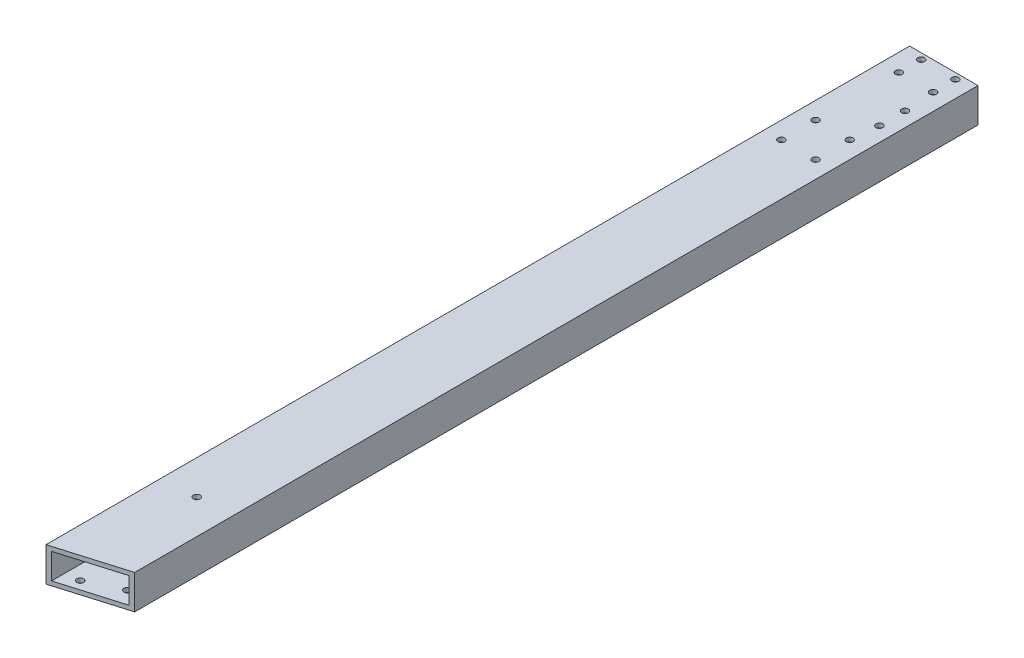
SolidWorks part; units mm, degrees
material "1060 Alloy"
ref_plane "Front Plane" through (0, 0, 0) normal (0, 0, 1) x (1, 0, 0)
ref_plane "Top Plane" through (0, 0, 0) normal (0, 1, 0) x (1, 0, 0)
ref_plane "Right Plane" through (0, 0, 0) normal (1, 0, 0) x (0, 0, -1)
sketch "Sketch1" plane through (0, 0, 0) normal (0, 0, 1) x (1, 0, 0)
  line L0 (-22.225, 9.525) -> (22.225, 9.525)
  line L2 (-25.4, 12.7) -> (25.4, 12.7)
  line L3 (-25.4, 12.7) -> (-25.4, -12.7)
  line L4 (-25.4, -12.7) -> (25.4, -12.7)
  line L5 (25.4, 12.7) -> (25.4, -12.7)
  line L10 (22.225, 9.525) -> (22.225, -9.525)
  line L11 (-22.225, -9.525) -> (22.225, -9.525)
  line L12 (-22.225, 9.525) -> (-22.225, -9.525)
  point P12 (0, 12.7)
  point P14 (25.4, 0)
  dimension "Wall Thickness" = 3.175
  dimension "Outside Width" = 50.8
  dimension "Outside Height" = 25.4
  dimension "Inside Height" = 19.05
  dimension "Inside Width" = 44.45
sketch "Sketch2" plane through (0, 0, 0) normal (1, 0, 0) x (0, 0, -1)
  line L0 (320.675, 0) -> (-320.675, 0)
  point P4 (0, 0)
  point P7 (-320.675, 0)
  point P10 (320.675, 0)
  dimension "Length" = 641.35
sketch "Sketch3" plane through (0, 0, 0) normal (0, 0, 1) x (1, 0, 0)
  line L21 (25.4, 12.7) -> (-25.4, 12.7)
  line L22 (25.4, -12.7) -> (25.4, 12.7)
  line L23 (-25.4, -12.7) -> (25.4, -12.7)
  line L24 (-25.4, 12.7) -> (-25.4, -12.7)
  line L25 (25.4, 12.7) -> (-25.4, 12.7)
  line L26 (25.4, -12.7) -> (25.4, 12.7)
  line L27 (-25.4, -12.7) -> (25.4, -12.7)
  line L28 (-25.4, 12.7) -> (-25.4, -12.7)
  line L29 (22.225, 9.525) -> (-22.225, 9.525)
  line L30 (22.225, -9.525) -> (22.225, 9.525)
  line L31 (-22.225, -9.525) -> (22.225, -9.525)
  line L32 (-22.225, 9.525) -> (-22.225, -9.525)
  line L33 (22.225, 9.525) -> (-22.225, 9.525)
  line L34 (22.225, -9.525) -> (22.225, 9.525)
  line L35 (-22.225, -9.525) -> (22.225, -9.525)
  line L36 (-22.225, 9.525) -> (-22.225, -9.525)
  dimension "D1" = 0
  dimension "D2" = 0
extrude "Boss-Extrude1" add sketch "Sketch3" along normal up to vertex (320.675 mm away) and the other way up to vertex (320.675 mm away) up to point (0, 0, 320.675) other way up to point (0, 0, -320.675)
sketch "Drawing Reference" plane through (0, 0, 0) normal (1, 0, 0) x (0, 0, -1)
  line L0 (-320.675, 0) -> (320.675, 0) construction
  line L1 (0, -12.7) -> (0, 12.7) construction
  line L2 (-320.675, -12.7) -> (320.675, -12.7) construction
  line L5 (-320.675, 12.7) -> (320.675, 12.7) construction
  point P7 (-284.099, 0)
  point P8 (284.099, 0)
  dimension "D1" = 36.576
sketch "Sketch4" plane through (0, 12.7, 0) normal (0, 1, 0) x (1, 0, 0)
  line L0 (-25.4, -320.675) -> (25.4, -305.6274)
  line L1 (25.4, -320.675) -> (25.4, 320.675) construction
  line L2 (25.4, -320.675) -> (-25.4, -320.675)
  dimension "D1" = 16.5
extrude "Cut-Extrude1" cut sketch "Sketch4" against normal through all and the other way through all flip side to cut
sketch "Sketch6" plane through (0, -12.7, 0) normal (0, -1, 0) x (1, 0, 0)
  line L0 (25.4, 305.6274) -> (22.1108, 294.5233) construction
  line L1 (25.4, 279.2824) -> (22.225, 279.2824) construction
  line L2 (25.4, 305.6274) -> (25.4, -320.675) construction
  line L3 (22.225, 279.2824) -> (22.225, 313.1512) construction
  line L4 (22.1108, 294.5233) -> (11.811, 297.5742) construction
  line L5 (-11.811, 250.3501) -> (-11.811, 328.3651) construction
  line L6 (-25.4, 320.675) -> (-27.5213, 313.5136) construction
  line L7 (-25.4, 287.6223) -> (-22.225, 287.6223) construction
  line L8 (-25.4, 320.675) -> (-25.4, -320.675) construction
  line L9 (-22.225, 287.6223) -> (-22.225, 328.3651) construction
  line L10 (-27.5213, 313.5136) -> (-11.811, 308.86) construction
  line L11 (11.811, 250.3501) -> (11.811, 313.1512) construction
  line L12 (-27.5213, 313.5136) -> (-36.5388, 283.071) construction
  line L13 (22.1108, 294.5233) -> (13.0933, 264.0807) construction
  line L14 (-37.6746, 250.3501) -> (48.6057, 250.3501) construction
  line L15 (-11.811, 287.6223) -> (-11.811, 328.3651) construction
  line L16 (11.811, 279.2824) -> (11.811, 313.1512) construction
  line L17 (-36.5388, 283.071) -> (-11.811, 275.7463) construction
  line L18 (13.0933, 264.0807) -> (11.811, 264.4606) construction
  dimension "D1" = 10.414
  dimension "D2" = 10.414
hole_wizard "#10 Clearance Hole1" positions "Sketch7" profile "Sketch8" hole size "#10" standard "ANSI Inch"
sketch "Sketch7" plane through (0, -12.7, 0) normal (0, -1, 0) x (-1, 0, 0)
  point P0 (-11.811, -264.4606)
  point P3 (11.811, -275.7463)
  point P7 (-11.811, -297.5742)
  point P10 (11.811, -308.86)
sketch "Sketch8" plane through (11.811, -12.7, 264.4606) normal (1, 0, 0) x (0, 0, -1)
  line L0 (0, 0) -> (0, 6.5757)
  line L1 (0, 6.5757) -> (2.4892, 5.08)
  line L2 (2.4892, 5.08) -> (2.4892, 0)
  line L5 (2.4892, 0) -> (0, 0)
  line L10 (0, 6.5757) -> (-2.4892, 5.08) construction
  line L11 (0, -6.35) -> (0, 107.95) construction
  dimension "Hole Dia." = 4.9784
  dimension "Hole Depth" = 5.08
  dimension "Drill Angle" = 118
sketch "Sketch9" plane through (0, 12.7, 0) normal (0, 1, 0) x (1, 0, 0)
  line L0 (-12.3709, 316.23) -> (-9.8309, 316.23) construction
  line L2 (-9.1044, 314.5662) -> (-9.0928, 314.5269) construction
  line L3 (10.4891, 316.23) -> (13.0291, 316.23) construction
  line L4 (13.0291, 299.72) -> (10.4891, 299.72) construction
  line L5 (-9.8309, 299.72) -> (-12.3709, 299.72) construction
hole_wizard "#10 Clearance Hole2" positions "Sketch10" profile "Sketch11" hole size "#10" standard "ANSI Inch"
sketch "Sketch10" plane through (0, 12.7, 0) normal (0, 1, 0) x (1, 0, 0)
  point P0 (13.0291, 299.72)
  point P3 (-12.3709, 299.72)
  point P6 (13.0291, 316.23)
  point P9 (-12.3709, 316.23)
sketch "Sketch11" plane through (13.0291, 12.7, -299.72) normal (1, 0, 0) x (0, 0, 1)
  line L0 (0, 0) -> (0, 6.5757)
  line L1 (0, 6.5757) -> (2.4892, 5.08)
  line L2 (2.4892, 5.08) -> (2.4892, 0)
  line L5 (2.4892, 0) -> (0, 0)
  line L10 (0, 6.5757) -> (-2.4892, 5.08) construction
  line L11 (0, -6.35) -> (0, 107.95) construction
  dimension "Hole Dia." = 4.9784
  dimension "Hole Depth" = 5.08
  dimension "Drill Angle" = 118
sketch "Sketch12" plane through (0, 12.7, 0) normal (0, 1, 0) x (1, 0, 0)
  line L0 (-12.7, 238.125) -> (12.7, 238.125) construction
  line L1 (12.7, 238.125) -> (12.7, 212.725) construction
  line L2 (12.7, 212.725) -> (-12.7, 212.725) construction
  line L3 (-12.7, 212.725) -> (-12.7, 238.125) construction
  point P4 (-12.3709, 240.6226)
hole_wizard "#10 Clearance Hole3" positions "Sketch13" profile "Sketch14" hole size "#10" standard "ANSI Inch" end condition through all
sketch "Sketch13" plane through (0, 12.7, 0) normal (0, 1, 0) x (1, 0, 0)
  point P0 (-12.7, 212.725)
  point P3 (12.7, 212.725)
  point P6 (12.7, 238.125)
  point P9 (-12.7, 238.125)
  point P12 (14.6226, 277.2519)
  point P15 (14.6226, 258.2019)
  point P18 (-12.3709, 240.665)
sketch "Sketch14" plane through (-12.7, 12.7, -212.725) normal (1, 0, 0) x (0, 0, 1)
  line L0 (0, 0) -> (0, 25.4)
  line L1 (0, 25.4) -> (2.4892, 25.4)
  line L2 (2.4892, 25.4) -> (2.4892, 0)
  line L5 (2.4892, 0) -> (0, 0)
  line L11 (0, -6.35) -> (0, 107.95) construction
  dimension "Thru Hole Dia." = 4.9784
  dimension "Thru Hole Depth" = 25.4
sketch "Sketch17" plane through (0, 12.7, 0) normal (0, 1, 0) x (1, 0, 0)
  point P0 (-0.0762, -234.0972)
hole_wizard "#10 Clearance Hole4" positions "Sketch15" profile "Sketch16" hole size "#10" standard "ANSI Inch" end condition through all
sketch "Sketch15" plane through (0, 12.7, 0) normal (0, 1, 0) x (1, 0, 0)
  point P0 (-0.0762, -234.0972)
sketch "Sketch16" plane through (-0.0762, 12.7, 234.0972) normal (1, 0, 0) x (0, 0, 1)
  line L0 (0, 0) -> (0, 25.4)
  line L1 (0, 25.4) -> (2.4892, 25.4)
  line L2 (2.4892, 25.4) -> (2.4892, 0)
  line L5 (2.4892, 0) -> (0, 0)
  line L11 (0, -6.35) -> (0, 107.95) construction
  dimension "Thru Hole Dia." = 4.9784
  dimension "Thru Hole Depth" = 25.4
equation "\"D1@Drawing Reference\"=\"Outside Width@Sketch1\" * 0.72"
